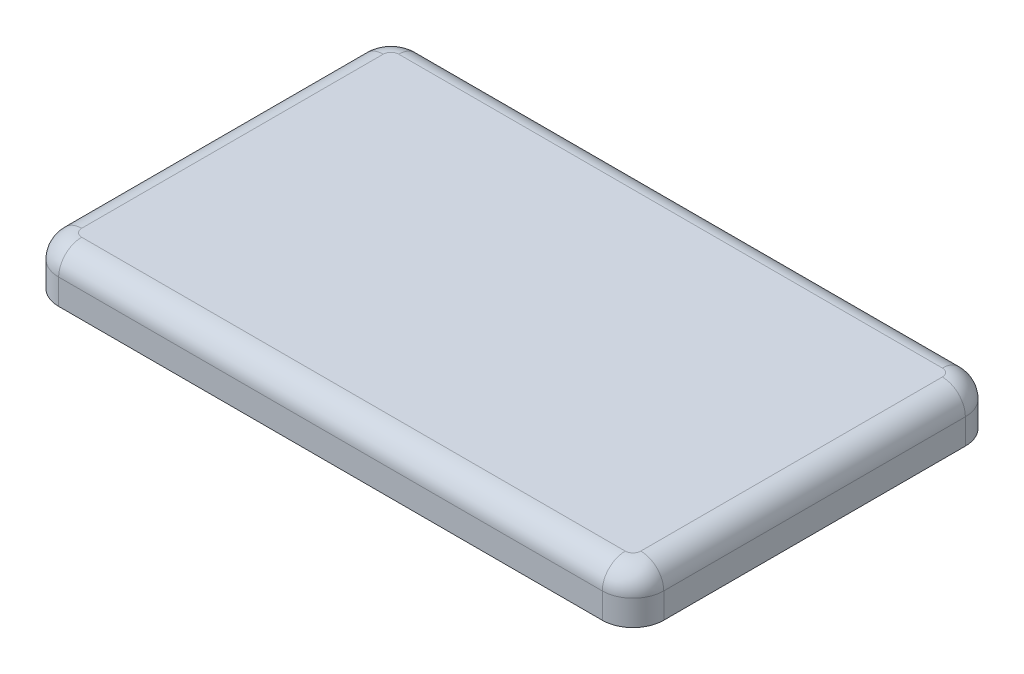
SolidWorks part; units mm, degrees
material "Balsa"
ref_plane "Front Plane" through (0, 0, 0) normal (0, 0, 1) x (1, 0, 0)
ref_plane "Top Plane" through (0, 0, 0) normal (0, 1, 0) x (1, 0, 0)
ref_plane "Right Plane" through (0, 0, 0) normal (1, 0, 0) x (0, 0, -1)
sketch "Sketch1" plane through (0, 0, 0) normal (0, 1, 0) x (1, 0, 0)
  line L1 (-125, 75) -> (125, 75)
  line L2 (-125, 75) -> (-125, -75)
  line L3 (-125, -75) -> (125, -75)
  line L4 (125, 75) -> (125, -75)
  line L5 (-125, 75) -> (125, -75) construction
  line L6 (-125, -75) -> (125, 75) construction
  point P0 (0, 0)
  dimension "D1" = 250
  dimension "D2" = 150
extrude "Boss-Extrude1" add sketch "Sketch1" against normal blind 20
fillet "Fillet1" radius 12.7 4 edges at (-125, -10, -75) (125, -10, -75) (-125, -10, 75) (125, -10, 75)
fillet "Fillet2" radius 9.5 8 edges at (-121.2803, 0, 71.2803) (-125, 0, 0) (-121.2803, 0, -71.2803) (0, 0, -75) (121.2803, 0, -71.2803) (125, 0, 0) (121.2803, 0, 71.2803) (0, 0, 75)
equation "\"Black_acrylic\"= 1.35mm"
equation "\"MDF_base\"= 20mm"
equation "\"D1@Boss-Extrude1\"=\"MDF_base\""
